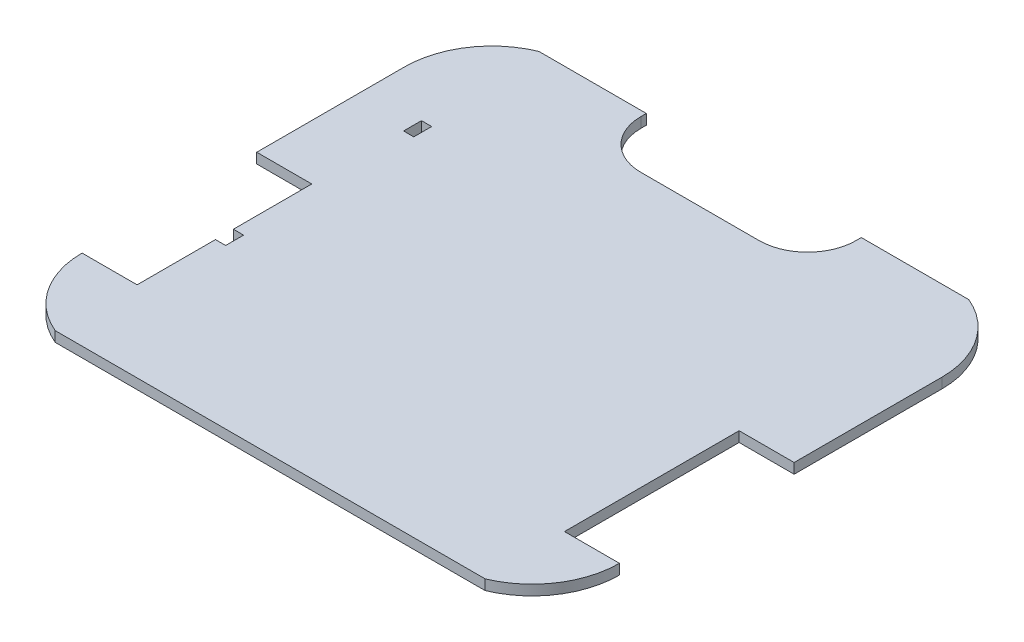
SolidWorks part; units mm, degrees
ref_plane "Front Plane" through (0, 0, 0) normal (0, 0, 1) x (1, 0, 0)
ref_plane "Top Plane" through (0, 0, 0) normal (0, 1, 0) x (1, 0, 0)
ref_plane "Right Plane" through (0, 0, 0) normal (1, 0, 0) x (0, 0, -1)
sketch "Sketch1" plane through (0, 0, 0) normal (0, 1, 0) x (1, 0, 0)
  line L1 (-127, 114.3) -> (127, 114.3)
  line L2 (-127, 114.3) -> (-127, -114.3)
  line L3 (-127, -114.3) -> (127, -114.3)
  line L4 (127, 114.3) -> (127, -114.3)
  line L5 (-127, 114.3) -> (127, -114.3) construction
  line L6 (-127, -114.3) -> (127, 114.3) construction
  point P0 (0, 0)
  dimension "D1" = 254
  dimension "D2" = 228.6
extrude "Boss-Extrude1" add sketch "Sketch1" along normal blind 4.826
sketch "Sketch2" plane through (0, 4.826, 0) normal (0, 1, 0) x (1, 0, 0)
  line L0 (-127, 114.3) -> (-127, -114.3) construction
  line L1 (-127, 6.35) -> (-101, 6.35)
  line L2 (-127, 6.35) -> (-127, -76.2)
  line L3 (-127, -76.2) -> (-101, -76.2)
  line L4 (-101, 6.35) -> (-101, -76.2)
  line L5 (127, -114.3) -> (127, 114.3) construction
  line L6 (127, 6.35) -> (101, 6.35)
  line L7 (127, 6.35) -> (127, -76.2)
  line L8 (127, -76.2) -> (101, -76.2)
  line L9 (101, 6.35) -> (101, -76.2)
  line L10 (-127, -114.3) -> (127, -114.3) construction
  dimension "D1" = 38.1
  dimension "D2" = 38.1
  dimension "D3" = 82.55
  dimension "D4" = 82.55
  dimension "D5" = 26
  dimension "D6" = 26
extrude "Cut-Extrude1" cut sketch "Sketch2" against normal blind 4.826
sketch "Sketch4" plane through (0, 4.826, 0) normal (0, 1, 0) x (1, 0, 0)
  line L0 (0, -114.3) -> (0, 114.3) construction
  line L1 (-127, -114.3) -> (127, -114.3) construction
  line L2 (127, 114.3) -> (-127, 114.3) construction
  line L3 (-127, 76.2) -> (-101.6, 76.2) construction
  line L4 (-127, 114.3) -> (-127, 6.35) construction
  line L5 (-101.6, 76.2) -> (-101.6, 114.3) construction
  line L6 (-127, 76.2) -> (-127, 114.3)
  line L7 (-127, 114.3) -> (-101.6, 114.3)
  line L8 (127, 76.2) -> (127, 114.3)
  line L9 (127, 114.3) -> (101.6, 114.3)
  arc A0 (-127, 76.2) -> (-101.6, 114.3) centre (-85.725, 76.2) cw
  arc A1 (127, 76.2) -> (101.6, 114.3) centre (85.725, 76.2) ccw
  dimension "D2" = 38.1
extrude "Cut-Extrude3" cut sketch "Sketch4" against normal blind 4.826
sketch "Sketch7" plane through (0, 4.826, 0) normal (0, 1, 0) x (1, 0, 0)
  line L0 (0, -114.3) -> (0, 114.3) construction
  line L1 (-127, -114.3) -> (127, -114.3) construction
  line L2 (101.6, 114.3) -> (-101.6, 114.3) construction
  line L3 (50.8, 88.9) -> (50.8, 114.3)
  line L4 (50.8, 88.9) -> (-50.8, 88.9)
  line L5 (0, 88.9) -> (0, 114.3)
  line L6 (50.8, 114.3) -> (-50.8, 114.3)
  line L7 (-50.8, 88.9) -> (-50.8, 114.3)
  line M6 (101.6, 114.3) -> (-101.6, 114.3)
extrude "Cut-Extrude5" cut sketch "Sketch7" against normal blind 4.826 contours L7 L4 L5 M6 | L5 L4 L3 M6 region at (25.4, 4.826, -101.6) region at (-25.4, 4.826, -101.6)
fillet "Fillet9" radius 22.86 1 edges at (-50.8, 2.413, -88.9) type face fillet first side face at (0, 2.413, -88.9) second side face at (-50.8, 2.413, -101.6)
fillet "Fillet10" radius 22.86 1 edges at (50.8, 2.413, -88.9) type face fillet first side face at (11.43, 2.413, -88.9) second side face at (50.8, 2.413, -101.6)
sketch "Sketch8" plane through (0, 4.826, 0) normal (0, 1, 0) x (1, 0, 0)
  line L0 (-127, -76.2) -> (-101.6, -76.2) construction
  line L1 (-101.6, -76.2) -> (-101.6, -114.3) construction
  line L2 (-127, -114.3) -> (127, -114.3) construction
  line L3 (-127, -76.2) -> (-127, -114.3)
  line L4 (-127, -114.3) -> (-101.6, -114.3)
  line L5 (0, -114.3) -> (0, 88.9) construction
  line L6 (27.94, 88.9) -> (-27.94, 88.9) construction
  line L7 (127, -114.3) -> (101.6, -114.3)
  line L8 (127, -76.2) -> (127, -114.3)
  arc A0 (-127, -76.2) -> (-101.6, -114.3) centre (-85.725, -76.2) ccw
  arc A1 (127, -76.2) -> (101.6, -114.3) centre (85.725, -76.2) cw
extrude "Cut-Extrude6" cut sketch "Sketch8" against normal blind 4.826
sketch "Sketch19" plane through (0, 4.826, 0) normal (0, 1, 0) x (1, 0, 0)
  line L0 (-101, -39.1583) -> (-101, -30.6917) construction
  line L1 (-101, -39.1583) -> (-96.174, -39.1583) construction
  line L2 (-96.174, -39.1583) -> (-96.174, -30.6917) construction
  line L3 (-101, -30.6917) -> (-96.174, -30.6917) construction
  line L4 (-101, 49.7417) -> (-101, 58.2083) construction
  line L5 (-101, 49.7417) -> (-96.174, 49.7417) construction
  line L6 (-96.174, 49.7417) -> (-96.174, 58.2083) construction
  line L7 (-101, 58.2083) -> (-96.174, 58.2083) construction
  line L8 (-101, -39.1583) -> (-101, -30.6917)
  line L9 (-101, -39.1583) -> (-96.174, -39.1583)
  line L10 (-96.174, -39.1583) -> (-96.174, -30.6917)
  line L11 (-101, -30.6917) -> (-96.174, -30.6917)
  line L12 (-101, 49.7417) -> (-101, 58.2083)
  line L13 (-101, 49.7417) -> (-96.174, 49.7417)
  line L14 (-96.174, 49.7417) -> (-96.174, 58.2083)
  line L15 (-101, 58.2083) -> (-96.174, 58.2083)
extrude "Cut-Extrude16" cut sketch "Sketch19" against normal through all
equation "\"MDF\"= 0.19in"
equation "\"GenDiameter\"= 60mm"
equation "\"GenCutDiameter\" = 1.8in"
equation "\"GenCutDistance\" = 1"
equation "\"TowerHeight\" = 6in"
equation "\"TowerFrontBase\" = 3in"
equation "\"FunnelHeight\" = 1in"
equation "\"FunnelAngle\" = 20"
equation "\"TowerSideBase\" = 3in"
equation "\"BaseLength\" = 9in"
equation "\"BaseWidth\" = 10in"
equation "\"WheelHoleLength\" = 3.25in"
equation "\"WheelHoleWidth\" = 26mm"
equation "\"DropLength\" = 1in"
equation "\"D1@Sketch1\"=\"BaseWidth\""
equation "\"D2@Sketch1\"=\"BaseLength\""
equation "\"D1@Boss-Extrude1\"=\"MDF\""
equation "\"WheelHoleFromBack\" = 1.5in"
equation "\"D1@Sketch2\"=\"WheelHoleFromBack\""
equation "\"D2@Sketch2\"=\"WheelHoleFromBack\""
equation "\"D3@Sketch2\"=\"WheelHoleLength\""
equation "\"D4@Sketch2\"=\"WheelHoleLength\""
equation "\"D5@Sketch2\"=\"WheelHoleWidth\""
equation "\"D6@Sketch2\"=\"WheelHoleWidth\""
equation "\"D1@Cut-Extrude1\"=\"MDF\""
equation "\"DropWidth\" = 8.5in"
equation "\"BumperWidth\" = 1in"
equation "\"D1@Sketch4\"=\"BumperWidth\""
equation "\"D2@Sketch4\"=\"WheelHoleFromBack\""
equation "\"D1@Cut-Extrude3\"=\"MDF\""
equation "\"D1@Sketch7\"=\"DropLength\""
equation "\"D2@Sketch7\"=\"DropWidthTop\"/2"
equation "\"D1@Cut-Extrude5\"=\"MDF\""
equation "\"D1@Sketch8\"=\"BumperWidth\""
equation "\"D1@Cut-Extrude6\"=\"MDF\""
equation "\"DropWidthTop\" = 4in"
